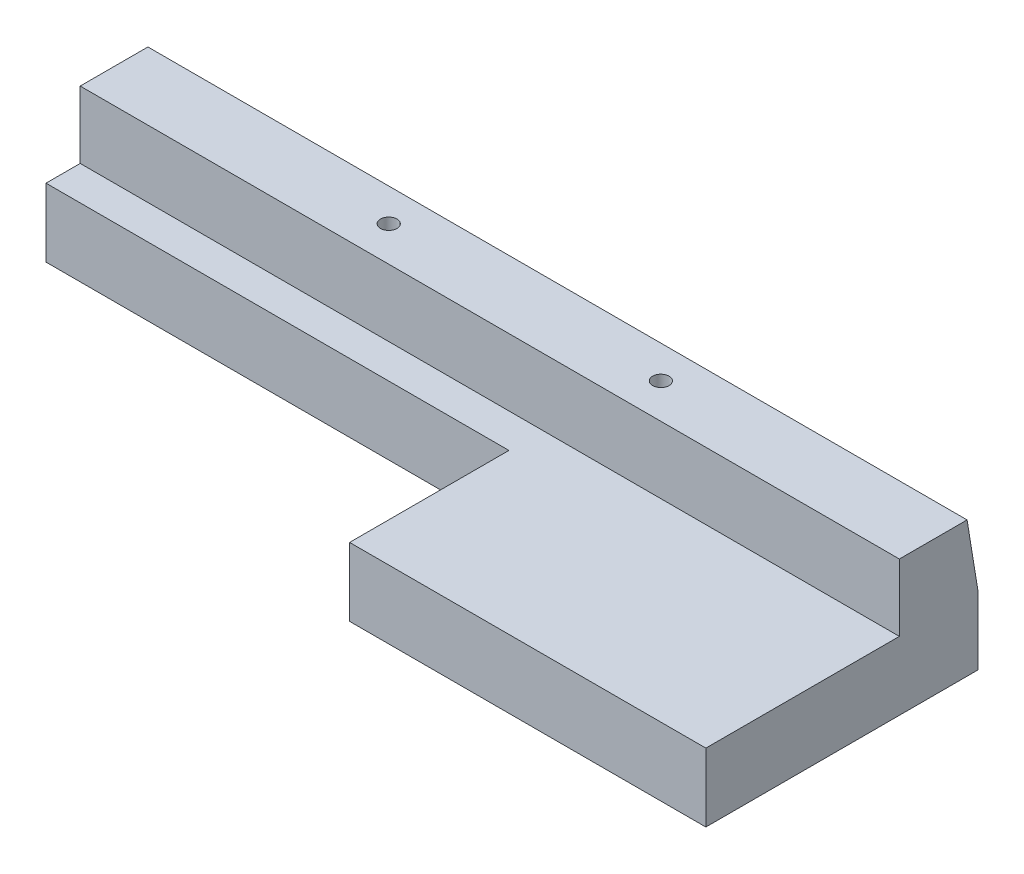
SolidWorks part; units mm, degrees
ref_plane "Płaszczyzna przednia" through (0, 0, 0) normal (0, 0, 1) x (1, 0, 0)
ref_plane "Płaszczyzna górna" through (0, 0, 0) normal (0, 1, 0) x (1, 0, 0)
ref_plane "Płaszczyzna prawa" through (0, 0, 0) normal (1, 0, 0) x (0, 0, -1)
sketch "Szkic1" plane through (0, 0, 0) normal (0, 0, 1) x (1, 0, 0)
  line L1 (-58.3066, 32.0248) -> (61.4934, 32.0248)
  line L2 (-58.3066, 32.0248) -> (-58.3066, 22.0248)
  line L3 (-58.3066, 22.0248) -> (61.4934, 22.0248)
  line L4 (61.4934, 32.0248) -> (61.4934, 22.0248)
  dimension "D1" = 119.8
  dimension "D2" = 10
extrude "Dodanie-wyciągnięcie2" add sketch "Szkic1" along normal blind 38.3 contours L2 L3 L4 L1
sketch "Szkic21" plane through (0, 32.0248, 0) normal (0, 1, 0) x (1, 0, 0)
  line L0 (61.4934, -38.3) -> (61.4934, 0) construction
  line L1 (-58.3066, 0) -> (61.4934, 0)
  line L2 (-58.3066, 0) -> (-58.3066, -10)
  line L3 (-58.3066, -10) -> (61.4934, -10)
  line L4 (61.4934, 0) -> (61.4934, -10)
extrude "Dodanie-wyciągnięcie3" add sketch "Szkic21" along normal blind 9.8
sketch "Szkic22" plane through (0, 22.0248, 0) normal (0, -1, 0) x (1, 0, 0)
  line L0 (-58.3066, 4.88) -> (-18.3066, 4.88) construction
  line L1 (-58.3066, 38.3) -> (-58.3066, 0) construction
  line L2 (-18.3066, 4.88) -> (21.4934, 4.88) construction
  line L3 (21.4934, 4.88) -> (61.4934, 4.88) construction
  line L4 (61.4934, 38.3) -> (61.4934, 0) construction
  line L5 (1.9729, 4.88) -> (1.9729, 0) construction
  line L6 (-58.3066, 0) -> (61.4934, 0) construction
hole_wizard "Pogłębienie walcowe pod M2 wkręt do części metalowych z łbem stożkowym ściętym2" positions "Szkic23" profile "Szkic24" counterbore size "M2" standard "Ansi Metric" end condition through all
sketch "Szkic23" plane through (0, 22.0248, 0) normal (0, -1, 0) x (-1, 0, 0)
  point P0 (-21.4934, -4.88)
  point P3 (18.3066, -4.88)
sketch "Szkic24" plane through (21.4934, 22.0248, 4.88) normal (1, 0, 0) x (0, 0, -1)
  line L0 (0, 0) -> (0, 19.8)
  line L1 (0, 19.8) -> (1.2, 19.8)
  line L3 (1.2, 19.8) -> (1.2, 1.6)
  line L4 (1.2, 1.6) -> (2.5, 1.6)
  line L5 (2.5, 1.6) -> (2.5, 0)
  line L7 (2.5, 0) -> (0, 0)
  line L11 (0, -6.35) -> (0, 107.95) construction
  dimension "Średnica otworu na wylot" = 2.4
  dimension "Głębokość otworu na wylot" = 19.8
  dimension "Średnica pogłębienia walcowego" = 5
  dimension "Głębokość pogłębienia walcowego" = 1.6
sketch "Szkic28" plane through (0, 22.0248, 0) normal (0, -1, 0) x (1, 0, 0)
  line L0 (36.4934, 0) -> (36.4934, 23.3) construction
  line L1 (-58.3066, 0) -> (61.4934, 0) construction
  line L2 (36.4934, 23.3) -> (61.4934, 23.3) construction
  line L3 (61.4934, 38.3) -> (61.4934, 0) construction
  line L4 (-58.3066, 38.3) -> (61.4934, 38.3) construction
  circle A0 centre (36.4934, 23.3) radius 11.1
  dimension "D1" = 15
extrude "Wytnij-wyciągnięcie1" cut sketch "Szkic28" against normal blind 7.2
sketch "Szkic31" plane through (61.4934, 0, 0) normal (1, 0, 0) x (0, 0, -1)
  line L0 (-10, 32.0248) -> (-10, 71.9248)
  line L2 (0, 41.2325) -> (0, 32.0248)
  line L6 (0, 41.8248) -> (0, 22.0248) construction
  line L8 (0, 32.0248) -> (1.5, 32.0248)
  line L10 (-10, 32.0248) -> (1.5, 32.0248)
  line L12 (-10, 71.9248) -> (-5, 71.9248)
  line L13 (-5, 71.9248) -> (1.5, 32.0248)
  line L14 (-0.4105, 43.7521) -> (0.2752, 39.543)
  line L15 (0.2752, 39.543) -> (3.3905, 40.0505)
  line L16 (3.3905, 40.0505) -> (-0.4105, 43.7521)
  line M5 (0, 22.0248) -> (0, 41.8248)
  line M6 (0, 41.8248) -> (-10, 41.8248)
extrude "Wytnij-wyciągnięcie4" cut sketch "Szkic31" against normal blind 124.8 contours L13 M6 M5 region at (61.4934, 41.6274, 0.0322)
extrude "Dodanie-wyciągnięcie5" add sketch "Szkic31<5>" against normal blind 119.8 contours L13 L8 M5 region at (61.4934, 35.0941, -0.5)
sketch "Szkic31<5>" plane through (61.4934, 0, 0) normal (1, 0, 0) x (0, 0, -1) same geometry as "Szkic31"
sketch "Szkic34" plane through (0, 0, 0) normal (0, 0, -1) x (-1, 0, 0)
  line L1 (-61.4934, 32.0248) -> (58.3066, 32.0248)
  line L2 (-61.4934, 32.0248) -> (-61.4934, 22.0248)
  line L3 (-61.4934, 22.0248) -> (58.3066, 22.0248)
  line L4 (58.3066, 32.0248) -> (58.3066, 22.0248)
extrude "Dodanie-wyciągnięcie6" add sketch "Szkic34" along normal blind 1.5
sketch "Szkic37" plane through (0, 32.0248, 0) normal (0, 1, 0) x (1, 0, 0)
  line L1 (61.4934, -38.3) -> (9.3934, -38.3)
  line L2 (61.4934, -38.3) -> (61.4934, -30)
  line L3 (61.4934, -30) -> (9.3934, -30)
  line L4 (9.3934, -38.3) -> (9.3934, -30)
mirror "Lustro2" about plane through (-58.3066, 22.0248, 38.3) normal (0, 1, 0) of bodies 125 144
move or copy body "Obiekt-Przenieś/Kopiuj1" bodies to move or copy 146 copy no translate (0, -36.7663, 0) parameters "D1"=0, "D2"=36.7663, "D3"=0
delete or keep bodies "Obiekt-Usuń/zachowaj 1" type delete bodies bodies 125
sketch "Szkic38" plane through (0, 0, 38.3) normal (0, 0, 1) x (1, 0, 0)
  line L0 (-58.3066, -24.7414) -> (61.4934, -24.7414) construction
  line L1 (-58.3066, -14.7414) -> (9.3934, -14.7414)
  line L2 (-58.3066, -14.7414) -> (-58.3066, -24.7414)
  line L3 (-58.3066, -24.7414) -> (9.3934, -24.7414)
  line L4 (9.3934, -14.7414) -> (9.3934, -24.7414)
extrude "Wytnij-wyciągnięcie5" cut sketch "Szkic38" against normal blind 23.3
mirror "Lustro3" of bodies 148
move or copy body "Obiekt-Przenieś/Kopiuj2" bodies to move or copy 149 copy no translate (0, 52.1563, 0) parameters "D1"=0, "D2"=52.1563, "D3"=0
delete or keep bodies "Obiekt-Usuń/zachowaj 2" type delete bodies bodies 148
sketch "Szkic39" plane through (0, 37.4149, 0) normal (0, -1, 0) x (1, 0, 0)
  line L0 (-58.3066, 8.5) -> (-33.3066, 8.5) construction
  line L2 (-33.3066, 8.5) -> (-8.3066, 8.5) construction
  line L3 (61.4934, -1.5) -> (-58.3066, -1.5) construction
  circle A0 centre (-45.8066, 8.5) radius 5.1
  circle A1 centre (-8.3066, 8.5) radius 5.1
  dimension "D1" = 10
extrude "Wytnij-wyciągnięcie6" cut sketch "Szkic39" against normal blind 4.1
